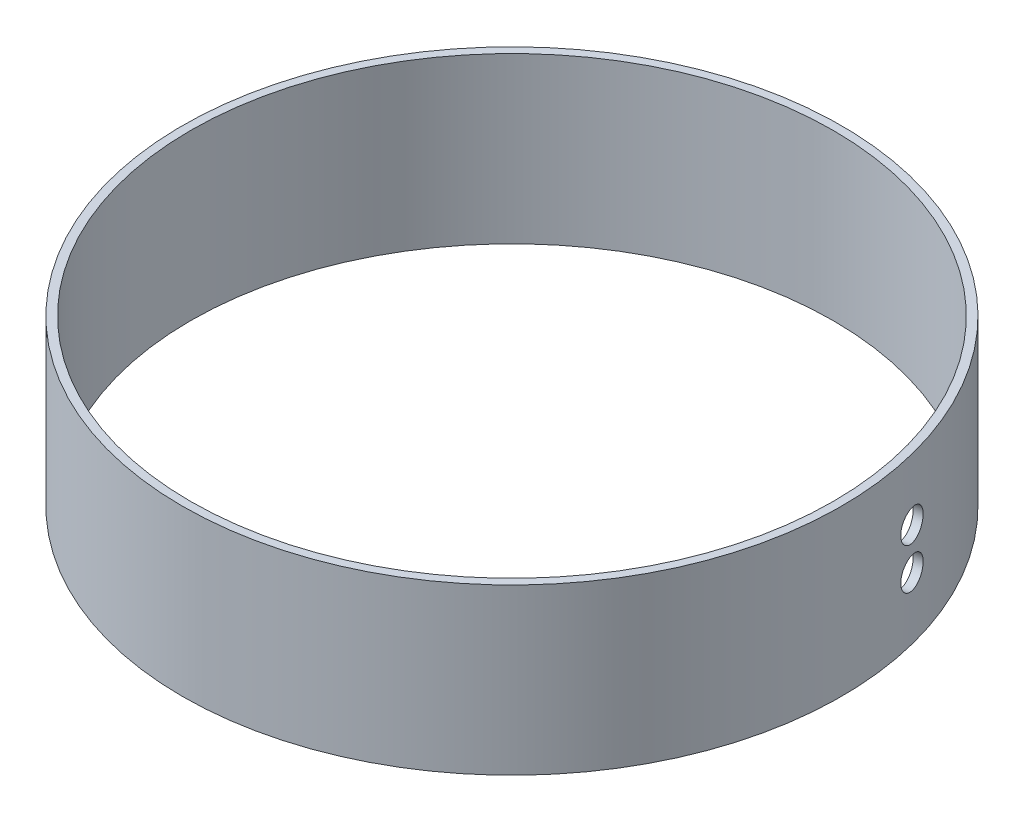
SolidWorks part; units mm, degrees
material "Wildman Fiberglass"
ref_plane "Front Plane" through (0, 0, 0) normal (0, 0, 1) x (1, 0, 0)
ref_plane "Top Plane" through (0, 0, 0) normal (0, 1, 0) x (1, 0, 0)
ref_plane "Right Plane" through (0, 0, 0) normal (1, 0, 0) x (0, 0, -1)
sketch "Sketch1" plane through (0, 0, 0) normal (0, 1, 0) x (1, 0, 0)
  circle A0 centre (0, 0) radius 49.53
  circle A1 centre (0, 0) radius 50.8
  dimension "D1" = 101.6
  dimension "D2" = 99.06
extrude "Boss-Extrude1" add sketch "Sketch1" along normal blind 25.4
extrude "Cut-Extrude1" cut sketch "Sketch2" against normal blind 25.4
sketch "Sketch2" plane through (80.7093, 206.3332, 111.646) normal (0.9693, 0, -0.2457) x (0, -1, 0)
  circle A0 centre (196.8082, 128.0554) radius 2.3813
  circle A1 centre (190.4582, 128.0554) radius 2.3813
  point P3 (0, 0)
  point P6 (0, 0)
  point P8 (0, 0)
equation "\"Length\"=1"
equation "\"D1@Boss-Extrude1\"=\"Length\""
